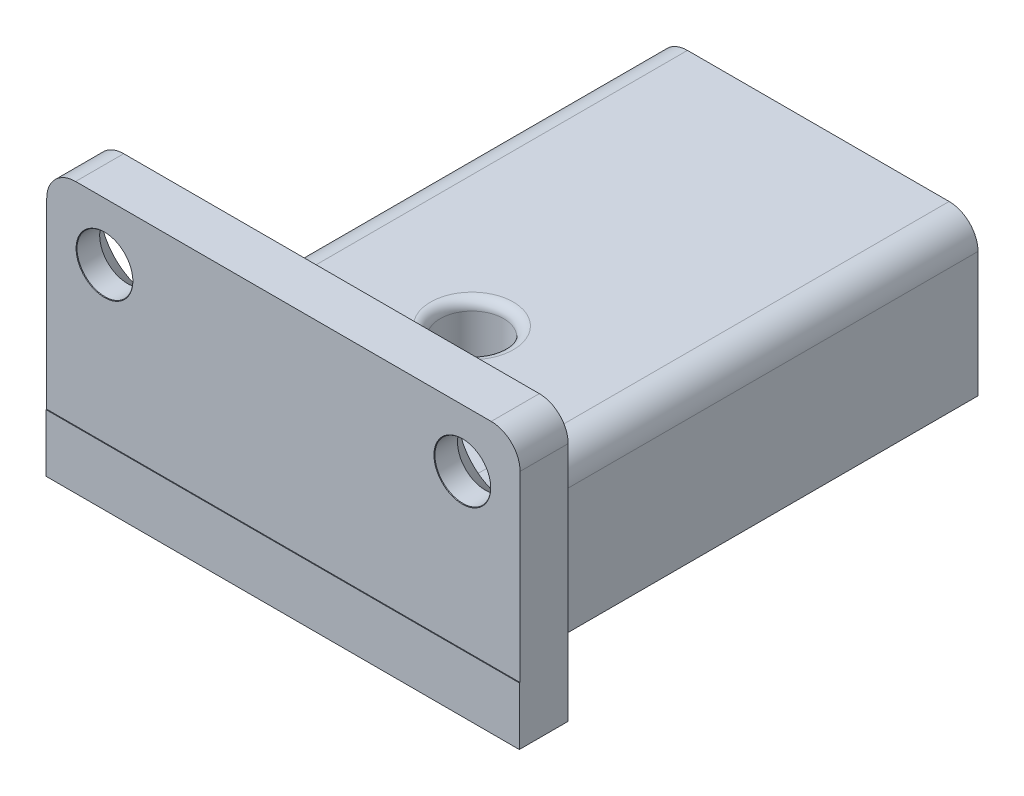
SolidWorks part; units mm, degrees
ref_plane "Plan de face" through (0, 0, 0) normal (0, 0, 1) x (1, 0, 0)
ref_plane "Plan de dessus" through (0, 0, 0) normal (0, 1, 0) x (1, 0, 0)
ref_plane "Plan de droite" through (0, 0, 0) normal (1, 0, 0) x (0, 0, -1)
sketch "Esquisse1" plane through (0, 0, 0) normal (0, 1, 0) x (1, 0, 0)
  line L0 (-6.3, 4.9618) -> (6.3, 4.9618)
  line L1 (-6.3, 4.9618) -> (-6.3, -7.8382)
  line L2 (6.3, 4.9618) -> (6.3, -7.8382)
  line L3 (-6.3, -7.8382) -> (6.3, -7.8382)
  line L4 (0, -7.8382) -> (0, 0) construction
  circle A0 centre (0, 1.9618) radius 1.65
  dimension "D4" = 3.3
  dimension "D1" = 12.8
  dimension "D2" = 12.6
  dimension "D3" = 9.8
extrude "Boss.-Extru.1" add sketch "Esquisse1" along normal blind 5
sketch "Esquisse2" plane through (0, 5, 0) normal (0, 1, 0) x (1, 0, 0)
  line L0 (-12.3, -7.8382) -> (12.3, -7.8382)
  line L1 (-12.3, -7.8382) -> (-12.3, -5.3382)
  line L2 (12.3, -7.8382) -> (12.3, -5.3382)
  line L3 (-12.3, -5.3382) -> (12.3, -5.3382)
  line L4 (-6.3, -7.8382) -> (6.3, -7.8382) construction
  line L6 (0, -7.8382) -> (0, 0.3118) construction
  line L7 (-6.3, 4.9618) -> (-6.3, -7.8382) construction
  line L8 (0, 1.9618) -> (0, 0.3118) construction
  circle A0 centre (0, 1.9618) radius 1.65 construction
  point P12 (0, 0.3118)
  point P13 (0, 1.9618)
  dimension "D1" = 6
  dimension "D2" = 2.5
extrude "Boss.-Extru.3" add sketch "Esquisse2" along normal blind 6 and the other way through all
sketch "Esquisse4" plane through (0, 0, 5.3382) normal (0, 0, -1) x (-1, 0, 0)
  line L0 (9.3, 0) -> (9.3, 8) construction
  line L1 (6.3, 0) -> (12.3, 0) construction
  line L2 (9.3, 8) -> (-9.3, 8) construction
  line L3 (-9.3, 8) -> (-9.3, 0) construction
  line L4 (-12.3, 0) -> (-6.3, 0) construction
  line L5 (0, 5) -> (0, 11) construction
  line L6 (-6.3, 5) -> (6.3, 5) construction
  line L7 (-12.3, 11) -> (12.3, 11) construction
  point P15 (0, 8)
  point P16 (0, 8)
hole_wizard "Fraisage pour vis à tête fraisée M2.51" positions "Esquisse3D1" profile "Esquisse5" countersink size "M2.5" standard "Ansi Metric" end condition through all
sketch3d "Esquisse3D1"
  point P0 (-9.3, 8, 5.3382)
  point P3 (9.3, 8, 5.3382)
sketch "Esquisse5" plane through (-9.3, 8, 5.3382) normal (1, 0, 0) x (0, 1, 0)
  line L0 (0, 0) -> (0, 2.5)
  line L1 (0, 2.5) -> (1.475, 2.5)
  line L2 (1.45, 2.475) -> (1.45, 1.3)
  line L3 (1.45, 1.3) -> (2.75, 0)
  line L5 (2.75, 0) -> (0, 0)
  line L6 (-1.45, 1.3) -> (-2.75, 0) construction
  line L7 (1.475, 2.5) -> (1.45, 2.475)
  line L8 (-1.475, 2.5) -> (-1.45, 2.475) construction
  line L11 (0, -6.35) -> (0, 107.95) construction
  dimension "Diamètre du perçage jusqu'au prochain" = 2.9
  dimension "Profondeur du perçage jusqu'au prochain" = 2.5
  dimension "Diamètre du fraisage entrant" = 5.5
  dimension "Angle du fraisage entrant" = 90
  dimension "Diamètre du fraisage débouchant" = 2.95
  dimension "Angle du fraisage débouchant" = 90
fillet "Congé1" [suppressed] radius 1
fillet "Congé2" [suppressed] radius 1
fillet "Congé3" radius 0.5 2 edges at (0, 0, -0.3118) (0, 5, -0.3118)
sketch "Esquisse6" plane through (0, 0, -4.9618) normal (0, 0, -1) x (-1, 0, 0)
  line L0 (6.3, 5) -> (-6.3, 5)
  line L1 (6.3, 5) -> (6.3, 2)
  line L2 (-6.3, 5) -> (-6.3, 2)
  line L3 (6.3, 2) -> (-6.3, 2)
  dimension "D1" = 3
extrude "Boss.-Extru.4" add sketch "Esquisse6" along normal blind 10
sketch "Esquisse7" plane through (0, 0, -14.9618) normal (0, 0, -1) x (-1, 0, 0)
  line L0 (-6.3, 5) -> (6.3, 5)
  line L1 (-6.3, 5) -> (-6.3, 0)
  line L2 (6.3, 5) -> (6.3, 0)
  line L3 (-6.3, 0) -> (6.3, 0)
  dimension "D1" = 5
extrude "Boss.-Extru.5" add sketch "Esquisse7" along normal blind 5
sketch "Esquisse9" plane through (0, 0, 0) normal (0, -1, 0) x (1, 0, 0)
  line L0 (12.3, 5.3382) -> (-12.3, 5.3382)
  line L1 (12.3, 5.3382) -> (12.3, 7.8769)
  line L2 (-12.3, 5.3382) -> (-12.3, 7.8769)
  line L3 (12.3, 7.8769) -> (-12.3, 7.8769)
extrude "Boss.-Extru.6" add sketch "Esquisse9" along normal blind 3
sketch "Esquisse11" plane through (0, 0, 5.3382) normal (0, 0, -1) x (-1, 0, 0)
  line L0 (-6.3, 5) -> (-6.3, -3)
  line L1 (-6.3, 5) -> (-8.3, 5)
  line L2 (-6.3, -3) -> (-8.3, -3)
  line L3 (-8.3, 5) -> (-8.3, -3)
  line L4 (12.3, -3) -> (-12.3, -3) construction
  line L6 (6.3, 5) -> (8.3, 5)
  line L7 (6.3, 5) -> (6.3, -3)
  line L8 (8.3, 5) -> (8.3, -3)
  line L9 (6.3, -3) -> (8.3, -3)
  point P16 (-12.225, -3)
  point P18 (12.225, -3)
  point P20 (0, 0)
  point P21 (0, 0)
  point P22 (0, 0)
  dimension "D1" = 2
extrude "Boss.-Extru.7" add sketch "Esquisse11" along normal up to surface (25.3 mm away) up to face at (0, 2.5, -19.9618)
fillet "Congé4" radius 1 3 edges at (0, 0, -14.9618) (0, 2, -14.9618) (0, 2, -4.9618)
fillet "Congé5" radius 1 2 edges at (-6.3, -3, -7.3118) (6.3, -3, -7.3118)
fillet "Congé6" radius 1.5 2 edges at (-8.3, 5, -7.3118) (8.3, 5, -7.3118)
fillet "Congé7" radius 1.5 2 edges at (12.3, 11, 6.5882) (-12.3, 11, 6.5882)
